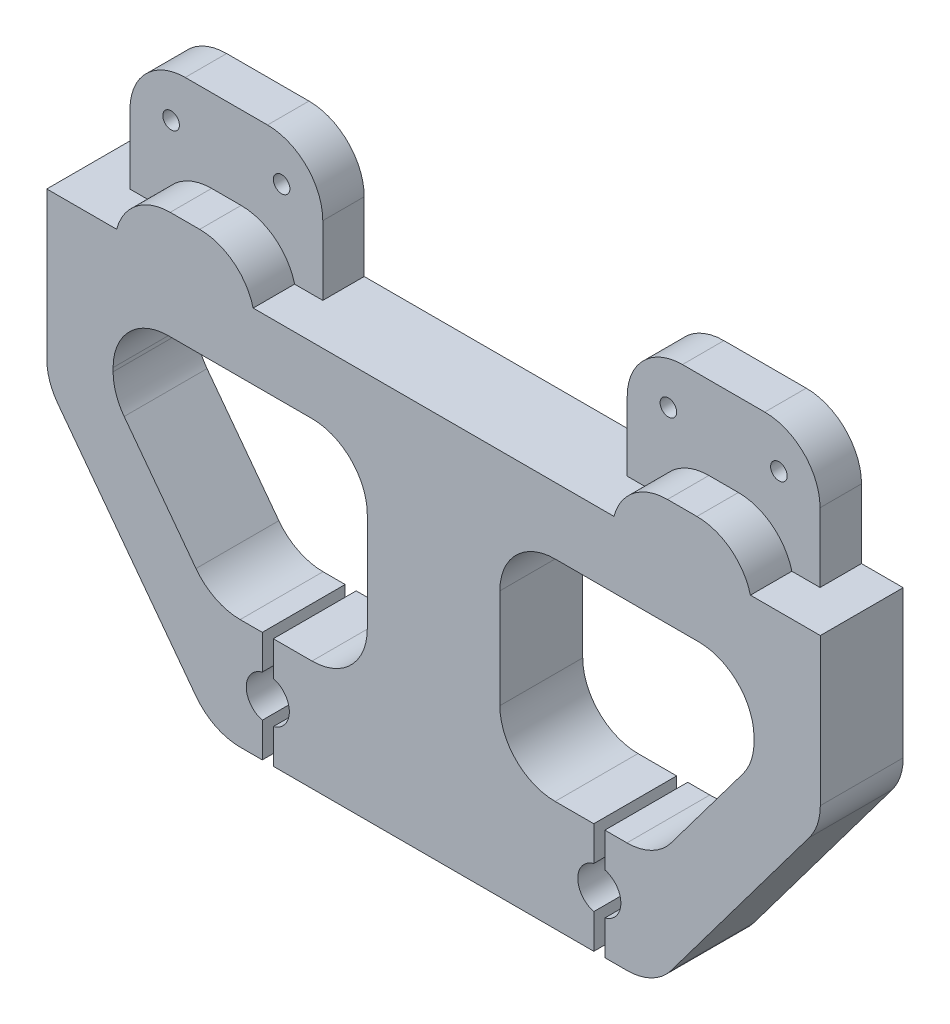
SolidWorks part; units mm, degrees
material "ABS"
ref_plane "Plan de face" through (0, 0, 0) normal (0, 0, 1) x (1, 0, 0)
ref_plane "Plan de dessus" through (0, 0, 0) normal (0, 1, 0) x (1, 0, 0)
ref_plane "Plan de droite" through (0, 0, 0) normal (1, 0, 0) x (0, 0, -1)
sketch "Esquisse1" plane through (0, 0, 0) normal (0, 0, 1) x (1, 0, 0)
  line L0 (45, 0) -> (-45, 0) construction
  line L1 (-62.45, 0) -> (-70, 0)
  line L3 (-27.55, 0) -> (-27.55, 22.5)
  line L4 (-27.55, 22.5) -> (-62.45, 22.5)
  line L5 (-62.45, 0) -> (-62.45, 22.5)
  line L6 (-27.55, -22.5) -> (-62.45, 22.5) construction
  line L7 (-27.55, 22.5) -> (-62.45, -22.5) construction
  line L8 (-27.55, 0) -> (0, 0)
  line L9 (-40, -70) -> (0, -70)
  line L10 (0, -70) -> (0, 0)
  line L11 (-70, 0) -> (-70, -30)
  line L12 (-62.45, -22.5) -> (-62.45, 0) construction
  line L13 (-27.55, -22.5) -> (-27.55, 0) construction
  line L14 (-62.45, -22.5) -> (-27.55, -22.5) construction
  line L15 (-70, -30) -> (-40, -70)
  line L16 (-70, -30) -> (-70, -70) construction
  line L17 (-70, -70) -> (-40, -70) construction
  point P4 (0, 0)
  dimension "D1" = 45
  dimension "D2" = 34.9
  dimension "D3" = 45
  dimension "D4" = 70
  dimension "D5" = 30
  dimension "D6" = 70
  dimension "D7" = 40
extrude "Boss.-Extru.1" add sketch "Esquisse1" along normal blind 7.5 and the other way blind 7.5 contours L10 L3 L4 L5 L9 region at (-33.5945, -25.3018, 0)
sketch "Esquisse3" plane through (0, 0, 0) normal (0, 0, 1) x (1, 0, 0)
  line L0 (0, 0) -> (-45, 0) construction
  line L2 (-32.65, -7.5) -> (-57.35, -7.5) construction
  line L3 (-32.65, 0) -> (-32.65, 7.5)
  line L4 (-32.65, 7.5) -> (-57.35, 7.5)
  line L5 (-57.35, 0) -> (-57.35, 7.5)
  line L6 (-45, 0) -> (-57.35, 7.5) construction
  line L7 (-32.65, 7.5) -> (-45, 0) construction
  line L8 (-62.45, 0) -> (-62.45, 22.5) construction
  line L10 (-45, 0) -> (-57.35, -7.5) construction
  line L11 (-32.65, -7.5) -> (-45, 0) construction
  line L12 (-32.65, -7.5) -> (-32.65, 0) construction
  line L13 (-57.35, -7.5) -> (-57.35, 0) construction
  line L14 (-57.35, 0) -> (-62.45, 0)
  line L15 (-62.45, 0) -> (-62.45, 22.5)
  line L16 (-62.45, 22.5) -> (-27.55, 22.5)
  line L17 (-27.55, 22.5) -> (-27.55, 0)
  line L18 (-27.55, 0) -> (-32.65, 0)
  dimension "D1" = 45
  dimension "D2" = 15
  dimension "D3" = 5.1
extrude "Enlèv. mat.-Extru.1" cut sketch "Esquisse3" along normal blind 7.5
fillet "Congé1" radius 10 4 edges at (-62.45, 22.5, -3.75) (-57.35, 7.5, 3.75) (-32.65, 7.5, 3.75) (-27.55, 22.5, -3.75)
fillet "Congé2" radius 10 2 edges at (-40, -70, 0) (-70, -30, 0)
sketch "Esquisse6" plane through (0, 0, 0) normal (0, 0, 1) x (1, 0, 0)
  line L0 (-58, -22) -> (-58, -22.6667)
  line L1 (-56, -28.6667) -> (-43, -46)
  line L2 (-35, -50) -> (-22, -50)
  line L3 (-12, -40) -> (-12, -22)
  line L4 (-22, -12) -> (-48, -12)
  line L5 (-70, 0) -> (-70, -26.6667) construction
  line L6 (-68, -32.6667) -> (-43, -66) construction
  line L7 (-35, -70) -> (0, -70) construction
  line L8 (0, -70) -> (0, 0) construction
  line L9 (-32.65, 0) -> (0, 0) construction
  arc A0 (-43, -46) -> (-35, -50) centre (-35, -40) ccw
  arc A1 (-22, -50) -> (-12, -40) centre (-22, -40) ccw
  arc A2 (-12, -22) -> (-22, -12) centre (-22, -22) ccw
  arc A3 (-58, -22) -> (-48, -12) centre (-48, -22) cw
  arc A4 (-58, -22.6667) -> (-56, -28.6667) centre (-48, -22.6667) ccw
  dimension "D6" = 10
  dimension "D1" = 12
  dimension "D2" = 12
  dimension "D3" = 20
  dimension "D4" = 12
  dimension "D5" = 12
extrude "Enlèv. mat.-Extru.3" cut sketch "Esquisse6" against normal through all and the other way through all
sketch "Esquisse5" plane through (0, 0, 0) normal (0, 0, 1) x (1, 0, 0)
  line L0 (0, 0) -> (0, -60) construction
  line L1 (0, -70) -> (0, 0) construction
  line L2 (0, -60) -> (-30, -60) construction
  line L3 (-30.311, -56.1124) -> (-31, -47.5) construction
  line L4 (-29, -72.5) -> (-31, -72.5)
  line L5 (-29, -72.5) -> (-29, -63.7696)
  line L6 (-29, -47.5) -> (-31, -47.5)
  line L7 (-31, -72.5) -> (-31, -63.7696)
  line L8 (-29, -72.5) -> (-29.689, -63.8876) construction
  line L9 (-29, -47.5) -> (-29.689, -56.1124) construction
  line L10 (-29.689, -56.1124) -> (-30, -60) construction
  line L11 (-30, -60) -> (-30.311, -63.8876) construction
  line L12 (-30.311, -63.8876) -> (-31, -72.5) construction
  line L13 (-29.689, -63.8876) -> (-30, -60) construction
  line L14 (-30, -60) -> (-30.311, -56.1124) construction
  line L15 (-31, -63.7696) -> (-31, -56.2304) construction
  line L16 (-31, -56.2304) -> (-31, -47.5)
  line L17 (-29, -60) -> (-29, -56.2304) construction
  line L18 (-29, -56.2304) -> (-29, -47.5)
  line L19 (-29, -63.7696) -> (-29, -60) construction
  arc A0 (-31, -56.2304) -> (-31, -63.7696) centre (-30, -60) ccw
  arc A1 (-30.311, -56.1124) -> (-31, -56.2304) centre (-30, -60) ccw construction
  arc A2 (-29.689, -56.1124) -> (-30.311, -56.1124) centre (-30, -60) ccw construction
  arc A3 (-29, -56.2304) -> (-29.689, -56.1124) centre (-30, -60) ccw construction
  arc A4 (-31, -63.7696) -> (-30.311, -63.8876) centre (-30, -60) ccw construction
  arc A5 (-29, -63.7696) -> (-29, -56.2304) centre (-30, -60) ccw
  arc A6 (-30.311, -63.8876) -> (-29.689, -63.8876) centre (-30, -60) ccw construction
  arc A7 (-29.689, -63.8876) -> (-29, -63.7696) centre (-30, -60) ccw construction
  dimension "D3" = 7.8
  dimension "D1" = 60
  dimension "D2" = 30
  dimension "D4" = 2
  dimension "D5" = 25
extrude "Enlèv. mat.-Extru.2" cut sketch "Esquisse5" against normal through all and the other way through all
sketch "Esquisse8" plane through (0, 0, 0) normal (0, 0, 1) x (1, 0, 0)
  line L0 (-45, 22.5) -> (-45, 14.5) construction
  line L1 (-37.55, 22.5) -> (-52.45, 22.5) construction
  line L2 (-45, 14.5) -> (-55, 14.5) construction
  circle A0 centre (-55, 14.5) radius 1.5
  circle A1 centre (-35, 14.5) radius 1.5
  dimension "D3" = 3
  dimension "D1" = 8
  dimension "D2" = 10
extrude "Enlèv. mat.-Extru.4" cut sketch "Esquisse8" against normal through all
mirror "Symétrie1" about plane through (0, 0, -7.5) normal (1, 0, 0) of bodies 106 102
